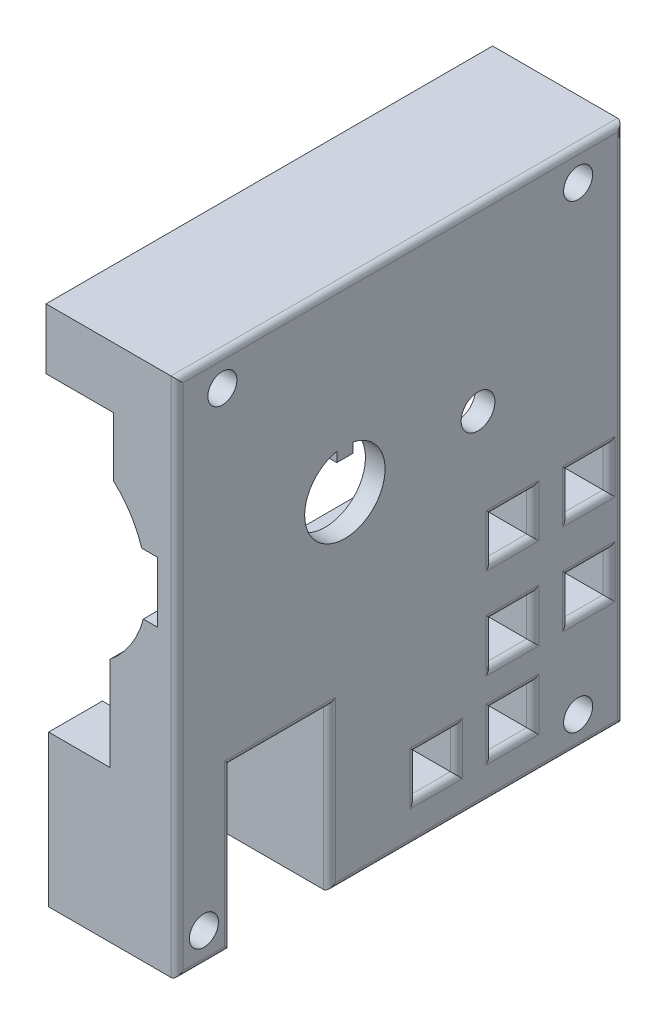
SolidWorks part; units mm, degrees
ref_plane "Front" through (0, 0, 0) normal (0, 0, 1) x (1, 0, 0)
ref_plane "Top" through (0, 0, 0) normal (0, 1, 0) x (1, 0, 0)
ref_plane "Right" through (0, 0, 0) normal (1, 0, 0) x (0, 0, -1)
sketch "Profile" plane through (0, 0, 0) normal (0, 0, 1) x (1, 0, 0)
  line L0 (-6.0107, -58.6279) -> (-6.0107, -33.6279)
  line L1 (-6.0107, -58.6279) -> (15.1893, -58.6279)
  line L2 (-6.4407, 17.4121) -> (-6.4407, 27.4121)
  line L3 (-6.4407, 27.4121) -> (15.1893, 27.4121)
  line L4 (15.1893, -58.6279) -> (15.1893, 27.4121)
  line L5 (-6.0107, -33.6279) -> (4.1393, -33.6279)
  line L6 (4.1393, -33.6279) -> (4.1393, -18.1379)
  line L7 (9.6313, -9.6379) -> (11.9493, -9.6379)
  line L8 (11.9493, -9.6379) -> (11.9493, 0.3621)
  line L9 (9.3593, 0.3621) -> (11.9493, 0.3621)
  line L10 (4.7093, 17.4121) -> (4.7093, 7.6371)
  line L11 (4.7093, 17.4121) -> (-6.4407, 17.4121)
  arc A0 (9.3593, 0.3621) -> (4.7093, 7.6371) centre (-6.1754, -4.4437) ccw
  arc A1 (4.1393, -18.1379) -> (9.6313, -9.6379) centre (-6.0948, -5.5013) ccw
  dimension "D14" = 16.261
  dimension "D17" = 16.261
  dimension "D2" = 10
  dimension "D3" = 2.59
  dimension "D4" = 2.318
  dimension "D5" = 9.775
  dimension "D6" = 11.15
  dimension "D7" = 15.49
  dimension "D8" = 10.15
  dimension "D9" = 25
  dimension "D10" = 21.2
  dimension "D11" = 86.04
  dimension "D12" = 21.63
  dimension "D13" = 10
  dimension "D15" = 23.99
  dimension "D16" = 5.492
extrude "ProfileExtrude" add sketch "Profile" along normal blind 73.76
sketch "HoseWindow" plane through (15.1893, 0, 0) normal (1, 0, 0) x (0, 0, -1)
  line L0 (-73.76, -58.6279) -> (0, -58.6279) construction
  line L1 (-64.87, -58.6279) -> (-48.58, -58.6279)
  line L2 (-64.87, -58.6279) -> (-64.87, -32.1279)
  line L3 (-64.87, -32.1279) -> (-48.58, -32.1279)
  line L4 (-48.58, -58.6279) -> (-48.58, -32.1279)
  line L5 (-73.76, -58.6279) -> (-73.76, 27.4121) construction
  dimension "D1" = 16.29
  dimension "D2" = 26.5
  dimension "D3" = 8.89
extrude "HoseWindowCut" cut sketch "HoseWindow" against normal through all
sketch "CageScrews" plane through (15.1893, 0, 0) normal (1, 0, 0) x (0, 0, -1)
  line L0 (-73.76, 27.4121) -> (0, 27.4121) construction
  line L1 (-73.76, -58.6279) -> (-73.76, 27.4121) construction
  line L2 (0, -58.6279) -> (0, 27.4121) construction
  line L3 (-48.58, -58.6279) -> (0, -58.6279) construction
  line L4 (-73.76, -58.6279) -> (-64.87, -58.6279) construction
  circle A0 centre (-66.26, 22.4121) radius 2.4
  circle A1 centre (-7.5, 22.4121) radius 2.4
  circle A2 centre (-7.5, -53.6279) radius 2.4
  circle A3 centre (-69.31, -53.6279) radius 2.4
  dimension "D1" = 4.8
  dimension "D2" = 4.8
  dimension "D3" = 4.8
  dimension "D4" = 4.8
  dimension "D5" = 5
  dimension "D6" = 7.5
  dimension "D7" = 7.5
  dimension "D8" = 5
  dimension "D9" = 5
  dimension "D10" = 7.5
  dimension "D11" = 5
  dimension "D12" = 4.45
extrude "CageScrewsCut" cut sketch "CageScrews" against normal through all
sketch "AxleHole" plane through (15.1893, 0, 0) normal (1, 0, 0) x (0, 0, -1)
  line L0 (-46.03, 2.3073) -> (-46.03, -9.2169) construction
  line L1 (-44.699, 2.3073) -> (-47.361, 2.3073)
  line L2 (-47.361, 2.3073) -> (-47.361, 3.9263)
  line L3 (-44.699, 2.3073) -> (-44.699, 3.9263)
  line L4 (-48.58, -58.6279) -> (0, -58.6279) construction
  line L5 (0, -58.6279) -> (0, 27.4121) construction
  arc A0 (-47.361, 3.9263) -> (-44.699, 3.9263) centre (-46.03, -2.5779) ccw
  dimension "D1" = 13.278
  dimension "D2" = 1.619
  dimension "D3" = 1.619
  dimension "D4" = 1.331
  dimension "D5" = 56.05
  dimension "D6" = 46.03
extrude "AxleHoleCut" cut sketch "AxleHole" against normal through all
sketch "SetScrews" plane through (15.1893, 0, 0) normal (1, 0, 0) x (0, 0, -1)
  line L0 (-46.03, -9.2169) -> (-46.03, -2.5779) construction
  circle A0 centre (-85.625, 3.1) radius 2.4263
  circle A1 centre (-24.0371, -2.0171) radius 2.7888
  arc A3 (-47.361, 3.9263) -> (-44.699, 3.9263) centre (-46.03, -2.5779) ccw construction
  dimension "D1" = 40
  dimension "D2" = 22
extrude "SetScrewsCut" cut sketch "SetScrews" against normal through all
sketch "Sketch1" plane through (15.1893, 0, 0) normal (1, 0, 0) x (0, 0, -1)
  line L0 (-21.7, -45.5779) -> (-21.7, -52.2779)
  line L1 (-21.7, -45.5779) -> (-15, -45.5779)
  line L2 (-21.7, -52.2779) -> (-15, -52.2779)
  line L3 (-15, -45.5779) -> (-15, -52.2779)
  line L4 (0, -58.6279) -> (0, 27.4121) construction
  line L5 (-48.58, -58.6279) -> (0, -58.6279) construction
  line L6 (-34.3, -45.5779) -> (-27.6, -45.5779)
  line L7 (-34.3, -52.2779) -> (-27.6, -52.2779)
  line L8 (-34.3, -45.5779) -> (-34.3, -52.2779)
  line L9 (-27.6, -45.5779) -> (-27.6, -52.2779)
  line L10 (-9.1, -32.8779) -> (-2.4, -32.8779)
  line L11 (-9.1, -39.5779) -> (-2.4, -39.5779)
  line L12 (-9.1, -32.8779) -> (-9.1, -39.5779)
  line L13 (-2.4, -32.8779) -> (-2.4, -39.5779)
  line L14 (-21.7, -32.8779) -> (-15, -32.8779)
  line L15 (-21.7, -39.5779) -> (-15, -39.5779)
  line L16 (-21.7, -32.8779) -> (-21.7, -39.5779)
  line L17 (-15, -32.8779) -> (-15, -39.5779)
  line L18 (-21.7, -45.5779) -> (-34.3, -45.5779) construction
  line L19 (-9.1, -17.8779) -> (-2.4, -17.8779)
  line L20 (-9.1, -24.5779) -> (-2.4, -24.5779)
  line L21 (-9.1, -17.8779) -> (-9.1, -24.5779)
  line L22 (-2.4, -17.8779) -> (-2.4, -24.5779)
  line L23 (-21.7, -17.8779) -> (-15, -17.8779)
  line L24 (-21.7, -24.5779) -> (-15, -24.5779)
  line L25 (-21.7, -17.8779) -> (-21.7, -24.5779)
  line L26 (-15, -17.8779) -> (-15, -24.5779)
  line L27 (-21.7, -32.8779) -> (-9.1, -32.8779) construction
  line L42 (-34.3, -32.8779) -> (-27.6, -32.8779) [skipped]
  line L43 (-34.3, -39.5779) -> (-27.6, -39.5779) [skipped]
  line L44 (-34.3, -32.8779) -> (-34.3, -39.5779) [skipped]
  line L45 (-27.6, -32.8779) -> (-27.6, -39.5779) [skipped]
  dimension "D1" = 15
  dimension "D2" = 6.7
  dimension "D3" = 6.7
  dimension "D4" = 6.35
  dimension "D5" = 12.6
  dimension "D6" = 12.6
extrude "Cut-Extrude1" cut sketch "Sketch1" against normal through all
fillet "Fillet1" radius 1 32 edges at (15.1893, -48.9279, 21.7) (15.1893, -52.2779, 18.35) (15.1893, -48.9279, 15) (15.1893, -45.5779, 18.35) (15.1893, -58.6279, 69.315) (15.1893, -45.3779, 64.87) (15.1893, -32.1279, 56.725) (15.1893, -45.3779, 48.58) (15.1893, -58.6279, 24.29) (15.1893, -15.6079, 0) (15.1893, 27.4121, 36.88) (15.1893, -15.6079, 73.76) (15.1893, -24.5779, 5.75) (15.1893, -21.2279, 2.4) (15.1893, -17.8779, 5.75) (15.1893, -21.2279, 9.1) (15.1893, -21.2279, 15) (15.1893, -17.8779, 18.35) (15.1893, -21.2279, 21.7) (15.1893, -24.5779, 18.35) (15.1893, -39.5779, 5.75) (15.1893, -36.2279, 2.4) (15.1893, -32.8779, 5.75) (15.1893, -36.2279, 9.1) (15.1893, -36.2279, 15) (15.1893, -32.8779, 18.35) (15.1893, -36.2279, 21.7) (15.1893, -39.5779, 18.35) (15.1893, -52.2779, 30.95) (15.1893, -48.9279, 27.6) (15.1893, -45.5779, 30.95) (15.1893, -48.9279, 34.3)
equation "\"CageRightBottomEdge\"=21.20mm"
equation "\"CageRightTopEdge\"=21.63mm"
equation "\"CageHeight\"=86.04mm"
equation "\"CageLength\"=73.76mm"
equation "\"CageTopScrewClearance\"=10mm"
equation "\"CageRightTopDepth\"= 11.15mm"
equation "\"CageRightBottomDepth\"=10.15mm"
equation "\"CageRightTopHeight\"=9.775mm"
equation "\"CageRightBottomHeight\"=15.49mm"
equation "\"CageRightTopChannelDepth\"=2.59mm"
equation "\"CageRightBottomChannelDepth\"=2.318mm"
equation "\"CageRightChannelHeight\"=10mm"
equation "\"CageChamberRadius\"=16.261mm"
equation "\"CageChanRelHeight\"=23.99mm"
equation "\"CageChanRelDepth\"=5.492mm"
equation "\"D2@Profile\" = \"CageRightChannelHeight\""
equation "\"D4@Profile\" = \"CageRightBottomChannelDepth\""
equation "\"D3@Profile\" = \"CageRightTopChannelDepth\""
equation "\"D5@Profile\" = \"CageRightTopHeight\""
equation "\"D7@Profile\" = \"CageRightBottomHeight\""
equation "\"CageBottomScrewClearance\"=25mm"
equation "\"D9@Profile\" = \"CageBottomScrewClearance\""
equation "\"D13@Profile\" = \"CageTopScrewClearance\""
equation "\"D8@Profile\" = \"CageRightBottomDepth\""
equation "\"D6@Profile\" = \"CageRightTopDepth\""
equation "\"D10@Profile\" = \"CageRightBottomEdge\""
equation "\"D12@Profile\" = \"CageRightTopEdge\""
equation "\"D11@Profile\" = \"CageHeight\""
equation "\"D15@Profile\" = \"CageChanRelHeight\""
equation "\"D16@Profile\" = \"CageChanRelDepth\""
equation "\"D17@Profile\" = \"CageChamberRadius\""
equation "\"D14@Profile\" = \"CageChamberRadius\""
equation "\"D1@ProfileExtrude\" = \"CageLength\""
equation "\"CageScrewDiameter\"=4.8mm"
equation "\"CageSetScrewDiameter\"=3.5mm"
equation "\"CageAxleRadius\"=6.639mm"
equation "\"CageAxleKeyHeight\"=1.619mm"
equation "\"CageAxleKeyWidth\"=2.662mm"
equation "\"CageHoseWindowWidth\"=16.29mm"
equation "\"CageHoseWindowHeight\"=26.5mm"
equation "\"CageHoseWindow-Edge\"=8.89mm"
equation "\"CageScrew-VerticalEdge\"=5.0mm"
equation "\"CageScrew-HorizontalEdge\"=7.5mm"
equation "\"CageScrew-HoseCornerScrewEdge\"=4.45mm"
equation "\"CageAxle-BottomEdge\"=56.05mm"
equation "\"CageAxle-FrontEdge\"=46.03mm"
equation "\"CageBackSetScrew-Axle\"=40mm"
equation "\"D1@HoseWindow\" = \"CageHoseWindowWidth\""
equation "\"D2@HoseWindow\" = \"CageHoseWindowHeight\""
equation "\"D3@HoseWindow\" = \"CageHoseWindow-Edge\""
equation "\"D6@CageScrews\"= \"CageScrew-HorizontalEdge\""
equation "\"D7@CageScrews\"= \"CageScrew-HorizontalEdge\""
equation "\"D10@CageScrews\"= \"CageScrew-HorizontalEdge\""
equation "\"D12@CageScrews\"= \"CageScrew-HoseCornerScrewEdge\""
equation "\"D5@CageScrews\"= \"CageScrew-VerticalEdge\""
equation "\"D8@CageScrews\"= \"CageScrew-VerticalEdge\""
equation "\"D11@CageScrews\"= \"CageScrew-VerticalEdge\""
equation "\"D9@CageScrews\"= \"CageScrew-VerticalEdge\""
equation "\"D1@CageScrews\"= \"CageScrewDiameter\""
equation "\"D2@CageScrews\"= \"CageScrewDiameter\""
equation "\"D4@CageScrews\"= \"CageScrewDiameter\""
equation "\"D3@CageScrews\"= \"CageScrewDiameter\""
equation "\"D1@AxleHole\" = \"CageAxleRadius\" * 2"
equation "\"D3@AxleHole\" = \"CageAxleKeyHeight\""
equation "\"D2@AxleHole\" = \"CageAxleKeyHeight\""
equation "\"D4@AxleHole\"= \"CageAxleKeyWidth\" / 2"
equation "\"D6@AxleHole\" = \"CageAxle-FrontEdge\""
equation "\"D5@AxleHole\" = \"CageAxle-BottomEdge\""
equation "\"D2@SetScrews\" = \"CageFrontSetScrew-Axle\""
equation "\"CageFrontSetScrew-Axle\"=22mm"
equation "\"D1@SetScrews\" = \"CageBackSetScrew-Axle\""
equation "\"TriggerSlot-FrontEdge\"=15mm"
equation "\"D1@Sketch1\" = \"TriggerSlot-FrontEdge\""
equation "\"TriggerSlotSize\"=6.7mm"
equation "\"D2@Sketch1\" = \"TriggerSlotSize\""
equation "\"D3@Sketch1\" = \"TriggerSlotSize\""
equation "\"TriggerSlot-BottomEdge\"=6.35mm"
equation "\"D4@Sketch1\" = \"TriggerSlot-BottomEdge\""
equation "\"CageLeftBottomEdge\"=21.15mm"
equation "\"CageLeftTopEdge\"=22.11mm"
equation "\"CageLeftTopDepth\"= 11.65mm"
equation "\"CageLeftBottomDepth\"=10.15mm"
equation "\"CageLeftTopHeight\"=10.56175mm"
equation "\"CageLeftBottomHeight\"=16mm"
equation "\"CageLeftTopChannelDepth\"=2.41908mm"
equation "\"CageLeftBottomChannelDepth\"=2.588mm"
equation "\"CageLeftChannelHeight\"=11.7mm"
equation "\"CageVelocityWindow-BackEdge\"=34.8mm"
equation "\"CageVelocityWindow-BottomEdge\"=27.55mm"
equation "\"CageVelocityWindowHeight\"=22.29mm"
equation "\"CageVelocityWindowWidth\"=12.61mm"
